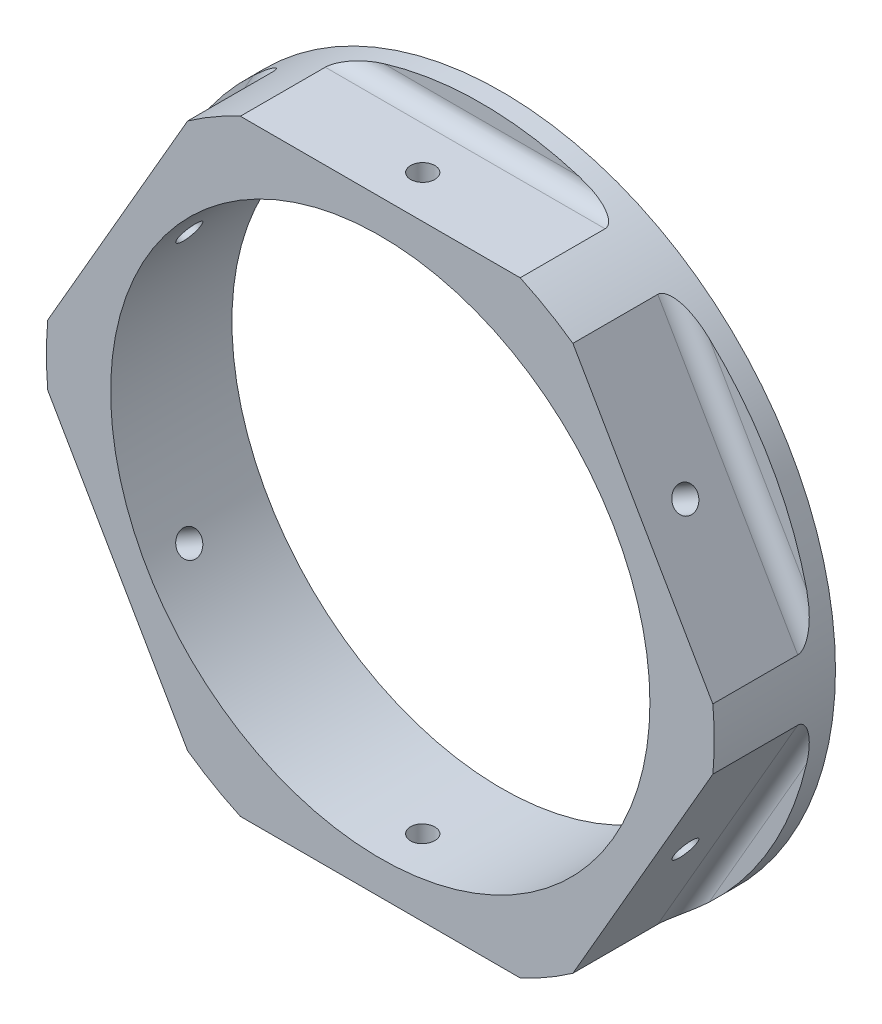
SolidWorks part; units mm, degrees
material "7075-T6, Płyta (SS)"
ref_plane "Płaszczyzna przednia" through (0, 0, 0) normal (0, 0, 1) x (1, 0, 0)
ref_plane "Płaszczyzna górna" through (0, 0, 0) normal (0, 1, 0) x (1, 0, 0)
ref_plane "Płaszczyzna prawa" through (0, 0, 0) normal (1, 0, 0) x (0, 0, -1)
sketch "Szkic2" plane through (0, 0, 0) normal (0, 0, 1) x (1, 0, 0)
  line L1 (21.6506, -37.5) -> (43.3013, 0)
  line L2 (43.3013, 0) -> (21.6506, 37.5)
  line L3 (21.6506, 37.5) -> (-21.6506, 37.5)
  line L4 (-21.6506, 37.5) -> (-43.3013, 0)
  line L5 (-43.3013, 0) -> (-21.6506, -37.5)
  line L6 (-21.6506, -37.5) -> (21.6506, -37.5)
  circle A0 centre (0, 0) radius 37.5 construction
  circle A1 centre (0, 0) radius 43.3013
  circle A2 centre (0, 0) radius 41.5
  circle A3 centre (0, 0) radius 46.0176
  dimension "D2" = 86.6025
  dimension "D3" = 83
  dimension "D1" = 75
extrude "Dodanie-wyciągnięcie1" add sketch "Szkic2" along normal blind 2.5 contours A1 | A3 region at (-44.716, 0, 0)
extrude "Dodanie-wyciągnięcie2" add sketch "Szkic2<3>" along normal blind 15 contours L5 L6 L1 L2 L3 L4 region at (0, 0, 0)
sketch "Szkic2<3>" plane through (0, 0, 0) normal (0, 0, 1) x (1, 0, 0) same geometry as "Szkic2"
sketch "Szkic3" plane through (0, 0, 2.5) normal (0, 0, -1) x (-1, 0, 0)
  circle A0 centre (0, 0) radius 42.5
  circle A8 centre (0, 0) radius 46.5
  dimension "D1" = 85
  dimension "D2" = 4
extrude "Wytnij-wyciągnięcie3" cut sketch "Szkic3" along normal blind 10
fillet "Zaokrąglenie1" [suppressed] radius 2
sketch "Szkic8" plane through (0, 0, 15) normal (0, 0, 1) x (1, 0, 0)
  circle A0 centre (0, 0) radius 33.35
  dimension "D1" = 66.7
extrude "Wytnij-wyciągnięcie2" cut sketch "Szkic8" against normal through all
cosmetic thread "Oznaczenie gwintu3" parameters "D2"=68
fillet "Zaokrąglenie2" radius 2 6 edges at (-32.476, 18.75, 2.5) (0, 37.5, 2.5) (32.476, 18.75, 2.5) (32.476, -18.75, 2.5) (0, -37.5, 2.5) (-32.476, -18.75, 2.5)
sketch "Szkic9" plane through (-32.476, -18.75, 0) normal (-0.866, -0.5, 0) x (0, 0, 1)
  line L0 (15, 17.7764) -> (15, -17.7764) construction
  circle A0 centre (9.75, 0) radius 1.5
  dimension "D1" = 5.25
  dimension "D2" = 3
extrude "Wytnij-wyciągnięcie4" cut sketch "Szkic9" against normal blind 10
pattern_circular "Szyk kołowy1" count 6 over 360 about axis through (0, 0, 15) along (0, 0, -1) of "Wytnij-wyciągnięcie4" reverse direction yes
sketch "Szkic10" plane through (0, 0, 15) normal (0, 0, 1) x (1, 0, 0)
  circle A0 centre (0, 0) radius 50
  circle A1 centre (0, 0) radius 41.3
  dimension "D1" = 100
  dimension "D2" = 82.6
extrude "Wytnij-wyciągnięcie5" cut sketch "Szkic10" against normal through all
